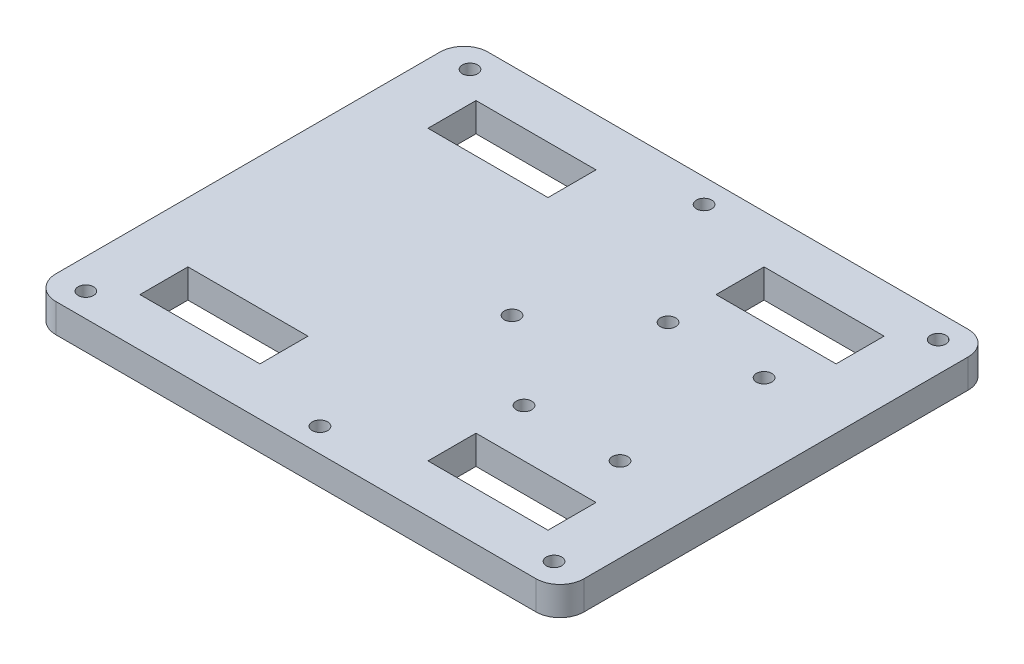
SolidWorks part; units mm, degrees
material "Maple"
ref_plane "Front Plane" through (0, 0, 0) normal (0, 0, 1) x (1, 0, 0)
ref_plane "Top Plane" through (0, 0, 0) normal (0, 1, 0) x (1, 0, 0)
ref_plane "Right Plane" through (0, 0, 0) normal (1, 0, 0) x (0, 0, -1)
sketch "Sketch1" plane through (0, 0, 0) normal (0, 1, 0) x (1, 0, 0)
  line L0 (-55, 0) -> (55, 0) construction
  line L1 (-55, 45) -> (55, 45)
  line L2 (-55, 45) -> (-55, -45)
  line L3 (-55, -45) -> (55, -45)
  line L4 (55, 45) -> (55, -45)
  point P0 (0, 0)
  dimension "D1" = 90
  dimension "D2" = 110
extrude "Boss-Extrude1" add sketch "Sketch1" along normal blind 6
sketch "Sketch2" plane through (0, 6, 0) normal (0, 1, 0) x (1, 0, 0)
  line L0 (-55, 0) -> (55, 0) construction
  line L1 (-55, 45) -> (-55, -45) construction
  line L2 (55, -45) -> (55, 45) construction
  line L3 (0, 0) -> (0, 45) construction
  line L4 (17.5, 35) -> (42.5, 35)
  line L5 (17.5, 35) -> (17.5, 25)
  line L6 (17.5, 25) -> (42.5, 25)
  line L7 (42.5, 35) -> (42.5, 25)
  line L8 (17.5, 35) -> (42.5, 25) construction
  line L9 (17.5, 25) -> (42.5, 35) construction
  line L10 (55, 45) -> (-55, 45) construction
  point P6 (30, 30)
  dimension "D1" = 10
  dimension "D2" = 60
  dimension "D3" = 60
  dimension "D4" = 25
extrude "Cut-Extrude1" cut sketch "Sketch2" against normal through all
mirror "Mirror1" about plane through (0, 0, 0) normal (0, 0, 1) of "Cut-Extrude1"
mirror "Mirror2" about plane through (0, 0, 0) normal (1, 0, 0) of "Mirror1", "Cut-Extrude1"
hole_wizard "M3 Clearance Hole1" positions "Sketch4" profile "Sketch3" hole size "M3" standard "ANSI Metric" end condition through all
sketch "Sketch4" plane through (0, 6, 0) normal (0, 1, 0) x (1, 0, 0)
  line L0 (13.7067, -15) -> (41.2933, -15) construction
  line L1 (13.7067, 15) -> (41.2933, 15) construction
  line L3 (17.5, 15) -> (17.5, -15) construction
  line L5 (37.5, 15) -> (37.5, -15) construction
  line L7 (27.5, 15) -> (27.5, -15) construction
  point P0 (17.5, 15)
  point P2 (37.5, 15)
  point P4 (17.5, -15)
  point P6 (37.5, -15)
  dimension "D2" = 20
sketch "Sketch3" plane through (17.5, 6, -15) normal (1, 0, 0) x (0, 0, 1)
  line L0 (0, 0) -> (0, 6)
  line L1 (0, 6) -> (1.6, 6)
  line L2 (1.6, 6) -> (1.6, 0)
  line L5 (1.6, 0) -> (0, 0)
  line L11 (0, -6.35) -> (0, 107.95) construction
  dimension "Thru Hole Dia." = 3.2
  dimension "Thru Hole Depth" = 6
hole_wizard "M3 Clearance Hole2" positions "Sketch6" profile "Sketch5" hole size "M3" standard "ANSI Metric" end condition through all
sketch "Sketch6" plane through (0, 6, 0) normal (0, 1, 0) x (1, 0, 0)
  line L0 (-48.75, -40) -> (-48.75, 40) construction
  line L1 (-48.75, 40) -> (48.75, 40) construction
  line L2 (48.75, 40) -> (48.75, -40) construction
  line L3 (48.75, -40) -> (-48.75, -40) construction
  line L5 (-48.75, 40) -> (48.75, -40) construction
  line L7 (-48.75, -40) -> (48.75, 40) construction
  line L9 (-30, 35) -> (-30, 40) construction
  line L10 (-42.5, 35) -> (-17.5, 35) construction
  line L11 (-30, 40) -> (-30, 45) construction
  line L12 (55, 45) -> (-55, 45) construction
  line L14 (-42.5, 30) -> (-48.75, 30) construction
  line L15 (-42.5, 25) -> (-42.5, 35) construction
  line L16 (-48.75, 30) -> (-55, 30) construction
  line L17 (-55, 45) -> (-55, -45) construction
  point P0 (48.75, 40)
  point P2 (0, 40)
  point P4 (-48.75, 40)
  point P6 (-48.75, -40)
  point P8 (0, -40)
  point P10 (48.75, -40)
  point P12 (0, 0)
sketch "Sketch5" plane through (48.75, 6, -40) normal (1, 0, 0) x (0, 0, 1)
  line L0 (0, 0) -> (0, 6)
  line L1 (0, 6) -> (1.6, 6)
  line L2 (1.6, 6) -> (1.6, 0)
  line L5 (1.6, 0) -> (0, 0)
  line L11 (0, -6.35) -> (0, 107.95) construction
  dimension "Thru Hole Dia." = 3.2
  dimension "Thru Hole Depth" = 6
fillet "Fillet1" radius 5 4 edges at (55, 3, 45) (-55, 3, 45) (55, 3, -45) (-55, 3, -45)
sketch "Sketch7" plane through (0, 6, 0) normal (0, 1, 0) x (1, 0, 0)
  line L0 (-200.184, 4.54) -> (-45, 4.54) construction
  line L1 (-200.184, 6.04) -> (-200.184, 3.04) construction
  line L2 (-55, 5.29) -> (-45, 5.29)
  line L3 (-55, 40) -> (-55, -40) construction
  line L4 (-45, 5.29) -> (-45, 3.79)
  line L5 (-45, 3.79) -> (-55, 3.79)
  line L6 (-55, 3.79) -> (-55, 5.29)
  dimension "D1" = 1.5
  dimension "D2" = 10
extrude "Cut-Extrude2" [suppressed] cut sketch "Sketch7" against normal through all
